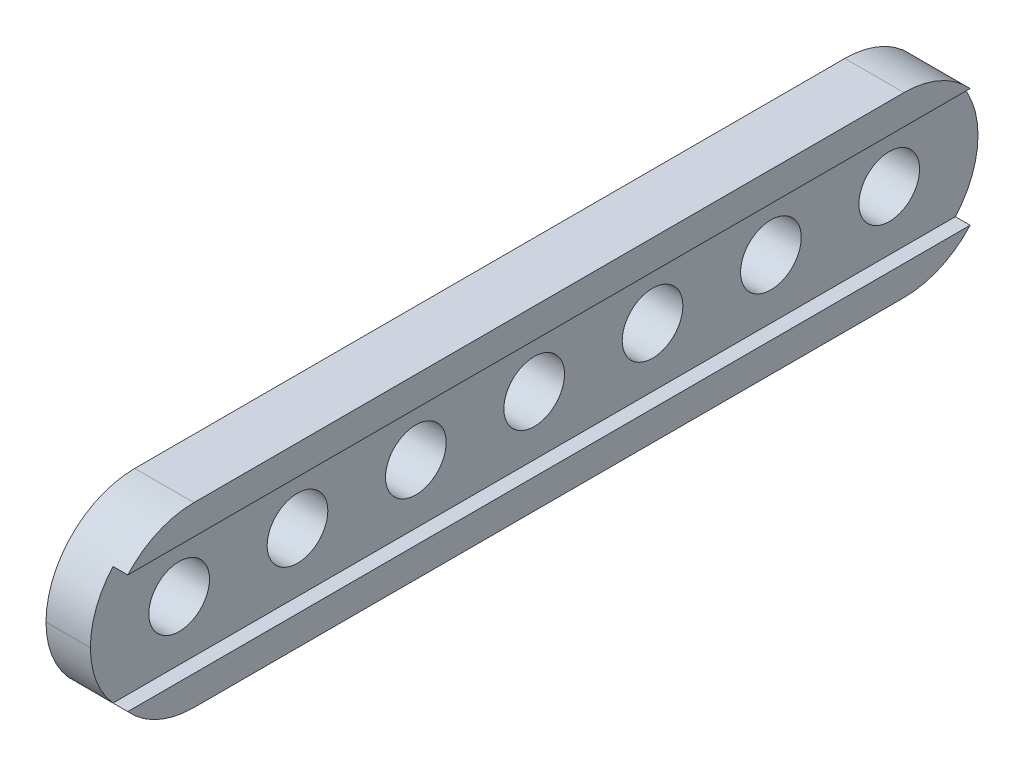
SolidWorks part; units mm, degrees
ref_plane "Front Plane" through (0, 0, 0) normal (0, 0, 1) x (1, 0, 0)
ref_plane "Top Plane" through (0, 0, 0) normal (0, 1, 0) x (1, 0, 0)
ref_plane "Right Plane" through (0, 0, 0) normal (1, 0, 0) x (0, 0, -1)
sketch "Sketch1" plane through (0, 0, 0) normal (0, 0, 1) x (1, 0, 0)
  line L0 (3, 6) -> (0, 6) construction
  line L1 (0, 0) -> (4, 0)
  line L2 (0, 0) -> (0, 12)
  line L3 (0, 12) -> (4, 12)
  line L4 (4, 0) -> (4, 2)
  line L5 (4, 10) -> (3, 10)
  line L7 (4, 2) -> (3, 2)
  line L8 (3, 10) -> (3, 2)
  line L9 (4, 10) -> (4, 12)
  dimension "D1" = 4
  dimension "D2" = 12
  dimension "D3" = 8
  dimension "D4" = 1
extrude "Boss-Extrude1" add sketch "Sketch1" against normal blind 60
ref_plane "Plane1" through (0, 0, -30) normal (0, 0, 1) x (1, 0, 0)
fillet "Fillet1" radius 6 4 edges at (2, 12, 0) (2, 0, 0) (2, 0, -60) (2, 12, -60)
sketch "Sketch2" plane through (0, 0, 0) normal (-1, 0, 0) x (0, 0, 1)
  circle A0 centre (-54, 6) radius 2.05
  dimension "D1" = 4.1
extrude "Cut-Extrude1" cut sketch "Sketch2" against normal through all
pattern_linear "LPattern1" count 4 spacing 8 along (0, 0, 1) of "Cut-Extrude1"
mirror "Mirror1" about plane through (0, 0, -30) normal (0, 0, 1) of "LPattern1", "Cut-Extrude1"
